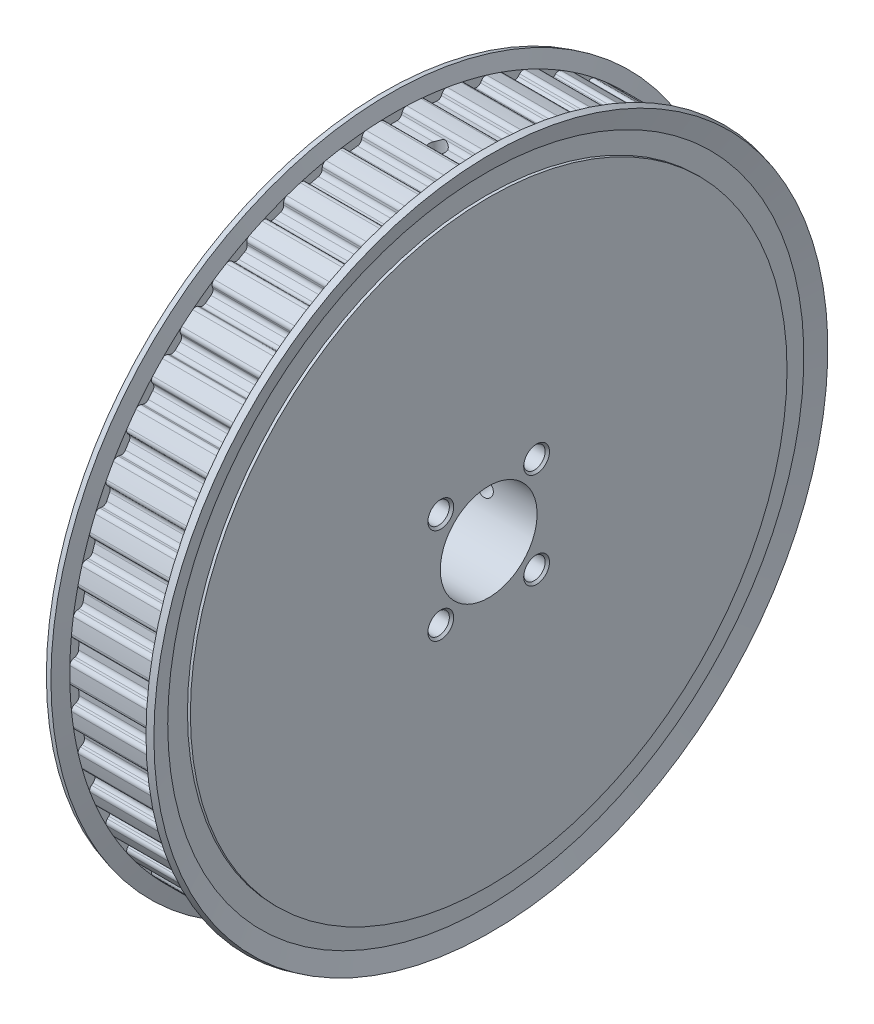
SolidWorks part; units mm, degrees
material "A6061"
ref_plane "前视基准面" through (0, 0, 0) normal (0, 0, 1) x (1, 0, 0)
ref_plane "上视基准面" through (0, 0, 0) normal (0, 1, 0) x (1, 0, 0)
ref_plane "右视基准面" through (0, 0, 0) normal (1, 0, 0) x (0, 0, -1)
sketch "草图1" plane through (0, 0, 0) normal (0, 0, 1) x (1, 0, 0)
  line L0 (0, 0) -> (0, 92.5)
  line L1 (0, 92.5) -> (0.9, 92.5)
  line L2 (0.9, 92.5) -> (0.9, 98.6239)
  line L3 (0.9, 98.6239) -> (-0.6698, 104.4824)
  line L4 (-0.6698, 104.4824) -> (1.2621, 105)
  line L5 (1.2621, 105) -> (2.5, 100.38)
  line L6 (2.5, 100.38) -> (29.5, 100.38)
  line L7 (29.5, 100.38) -> (30.7379, 105)
  line L8 (30.7379, 105) -> (32.6698, 104.4824)
  line L9 (32.6698, 104.4824) -> (31.1, 98.6239)
  line L10 (31.1, 98.6239) -> (31.1, 92.5)
  line L11 (31.1, 92.5) -> (32, 92.5)
  line L12 (32, 92.5) -> (32, 0)
  line L13 (32, 0) -> (0, 0)
  line L14 (32, 0) -> (0, 0) construction
revolve "旋转1" add sketch "草图1" angle 360 about L14 reverse direction yes
sketch "草图2" plane through (0, 0, 0) normal (0, 0, 1) x (1, 0, 0)
  line L0 (0, 0) -> (0, 15)
  line L1 (0, 15) -> (32, 15)
  line L2 (32, 15) -> (32, 0)
  line L3 (32, 0) -> (0, 0)
  line L4 (32, 0) -> (0, 0) construction
revolve "切除-旋转1" cut sketch "草图2" angle 360 about L4 reverse direction yes
ref_plane "基准面1" through (2.5, 0, 0) normal (1, 0, 0) x (0, 0, -1)
sketch "草图3" plane through (2.5, 0, 0) normal (1, 0, 0) x (0, 0, -1)
  line L0 (-2.701, 99.3634) -> (-2.4782, 98.7512)
  line L1 (2.4782, 98.7512) -> (2.701, 99.3634)
  line L2 (4.0933, 100.2965) -> (4.0933, 133.84)
  line L3 (4.0933, 133.84) -> (-4.0933, 133.84)
  line L4 (-4.0933, 133.84) -> (-4.0933, 100.2965)
  arc A0 (-4.0933, 100.2965) -> (-2.701, 99.3634) centre (-4.0354, 98.8777) cw
  arc A1 (-2.4782, 98.7512) -> (-1.0806, 97.784) centre (-1.0969, 99.2539) ccw
  arc A2 (-1.0806, 97.784) -> (1.0806, 97.784) centre (0, 0) cw
  arc A3 (1.0806, 97.784) -> (2.4782, 98.7512) centre (1.0969, 99.2539) ccw
  arc A4 (2.701, 99.3634) -> (4.0933, 100.2965) centre (4.0354, 98.8777) cw
extrude "切除-拉伸1" cut sketch "草图3" along normal blind 27
sketch "草图4" plane through (2.5, 0, 0) normal (1, 0, 0) x (0, 0, -1)
  point P0 (0, 0)
ref_axis "Pattern 4" through (2.5, 0, 0) along (1, 0, 0)
pattern_circular "阵列(圆周)1" count 50 every 7.2 about axis through (2.5, 0, 0) along (1, 0, 0) of "切除-拉伸1"
ref_plane "基准面2" through (16, 0, 0) normal (1, 0, 0) x (0, 0, -1)
sketch "草图5" plane through (16, 0, 0) normal (1, 0, 0) x (0, 0, -1)
  line L0 (0, 100.38) -> (2.4585, 100.38)
  line L1 (2.4585, 100.38) -> (2.4585, 0)
  line L2 (2.4585, 0) -> (0, 0)
  line L3 (0, 0) -> (0, 100.38)
  line L4 (0, 0) -> (0, 100.38) construction
revolve "切除-旋转2" cut sketch "草图5" angle 360 about L4 reverse direction yes
cosmetic thread "装饰螺纹线1" parameters "D1"=83.9029, "D2"=6
sketch "草图6" plane through (16, 0, 0) normal (1, 0, 0) x (0, 0, -1)
  line L0 (100.1819, -6.3029) -> (100.0276, -8.7566)
  line L1 (100.0276, -8.7566) -> (-0.1544, -2.4536)
  line L2 (-0.1544, -2.4536) -> (0, 0)
  line L3 (0, 0) -> (100.1819, -6.3029)
  line L4 (0, 0) -> (100.1819, -6.3029) construction
revolve "切除-旋转3" cut sketch "草图6" angle 360 about L4 reverse direction yes
ref_plane "基准面3" through (0, 0, 0) normal (0, -0.7071, 0.7071) x (1, 0, 0)
sketch "草图7" plane through (0, 0, 0) normal (0, -0.7071, 0.7071) x (1, 0, 0)
  line L0 (-7.0765, 21) -> (-5.1576, 24.3235)
  line L1 (-5.1576, 24.3235) -> (31.3235, 24.3235)
  line L2 (31.3235, 24.3235) -> (32, 25)
  line L3 (32, 25) -> (32, 21)
  line L4 (32, 21) -> (-7.0765, 21)
  line L5 (32, 21) -> (-7.0765, 21) construction
  dimension "D1" = 60
revolve "切除-旋转4" cut sketch "草图7" angle 360 about L5 reverse direction yes
cosmetic thread "装饰螺纹线2" parameters "D1"=32, "D2"=8
ref_plane "基准面4" through (32, 0, 0) normal (1, 0, 0) x (0, 0, -1)
sketch "草图8" plane through (32, 0, 0) normal (1, 0, 0) x (0, 0, -1)
  line L0 (-14.8492, 14.8492) -> (14.8492, 14.8492)
  line L1 (-14.8492, 14.8492) -> (-14.8492, -14.8492)
pattern_linear "阵列(线性)1" count 2 spacing 29.6985 along (0, 0, -1) count 2 spacing 29.6985 along (0, -1, 0) of "切除-旋转4"
ref_plane "基准面5" through (0, 0, 0) normal (0, 1, 0) x (1, 0, 0)
ref_plane "基准面6" through (0, 0, 0) normal (0, -0.866, 0.5) x (-1, 0, 0)
ref_plane "基准面7" through (0, 0, 0) normal (0, 1, 0) x (1, 0, 0)
ref_plane "基准面8" through (0, 15, 0) normal (0, 1, 0) x (1, 0, 0)
ref_plane "基准面9" through (0, 0, 0) normal (0, -0.0628, -0.998) x (-1, 0, 0)
ref_plane "基准面10" through (0, -0.9419, -14.9704) normal (0, -0.0628, -0.998) x (-1, 0, 0)
ref_plane "to_s1 XY" through (0, 15, 0) normal (0, 1, 0) x (1, 0, 0)
ref_plane "to_s1 XZ" through (0, 0, 0) normal (0, 0, 1) x (1, 0, 0)
ref_plane "to_s1 YZ" through (16, 0, 0) normal (1, 0, 0) x (0, 0, -1)
ref_axis "to_s1 X" through (-80.9, 15, 0) along (1, 0, 0)
ref_axis "to_s1 Y" through (16, 15, 50) along (0, 0, -1)
ref_axis "to_s1 Z" through (16, 50, 0) along (0, -1, 0)
sketch3d "to_s1"
  point P0 (16, 15, 0)
ref_plane "to_s2 XY" through (0, -0.9419, -14.9704) normal (0, -0.0628, -0.998) x (-1, 0, 0)
ref_plane "to_s2 XZ" through (0, 0, 0) normal (0, 0.998, -0.0628) x (1, 0, 0)
ref_plane "to_s2 YZ" through (16, 0, 0) normal (1, 0, 0) x (0, 0, -1)
ref_axis "to_s2 X" through (-80.9, -0.9419, -14.9704) along (1, 0, 0)
ref_axis "to_s2 Y" through (16, 48.9595, -18.1099) along (0, -0.998, 0.0628)
ref_axis "to_s2 Z" through (16, -5.0898, -80.9) along (0, 0.0628, 0.998)
sketch3d "to_s2"
  point P0 (16, -0.9419, -14.9704)
sketch "辅助圆" plane through (32, 0, 0) normal (1, 0, 0) x (0, 0, -1)
  circle A0 centre (0, 0) radius 104.4824
